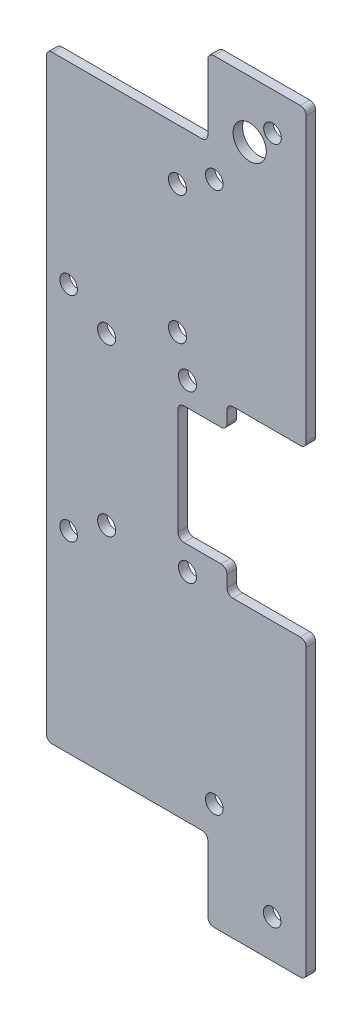
SolidWorks part; units mm, degrees
material "Thornel Mat VMA"
ref_plane "Front Plane" through (0, 0, 0) normal (0, 0, 1) x (1, 0, 0)
ref_plane "Top Plane" through (0, 0, 0) normal (0, 1, 0) x (1, 0, 0)
ref_plane "Right Plane" through (0, 0, 0) normal (1, 0, 0) x (0, 0, -1)
sketch "Sketch1" plane through (0, 0, 0) normal (0, 0, 1) x (1, 0, 0)
  line L0 (-2.9301, -104.5098) -> (-3.3149, -104.5098)
  line L1 (-3.3149, -72.8868) -> (-2.9301, -72.8868)
  line L78 (45.3299, -66.5368) -> (45.3299, -72.8868)
  line L79 (45.3299, -104.5098) -> (45.3299, -110.8598)
  line L80 (66.5174, -66.5368) -> (105.3971, 12.1397)
  line L81 (105.3971, 12.1397) -> (38.7094, 12.1397)
  line L88 (38.7094, 12.1397) -> (38.7094, -8.6883)
  line L89 (-2.9301, -8.6883) -> (38.7094, -8.6883)
  line L90 (-3.3149, -53.8368) -> (-2.9301, -53.8368)
  line L91 (-2.9301, -53.8368) -> (-2.9301, -8.6883)
  line L92 (-3.3149, -66.5368) -> (-3.3149, -53.8368)
  line L93 (-3.3149, -72.8868) -> (-3.3149, -66.5368)
  line L94 (-2.9301, -104.5098) -> (-2.9301, -72.8868)
  line L95 (-3.3149, -110.8598) -> (-3.3149, -104.5098)
  line L96 (66.5174, -110.8598) -> (105.3971, -189.5363)
  line L97 (105.3971, -189.5363) -> (38.7094, -189.5363)
  line L98 (38.7094, -189.5363) -> (38.7094, -168.7083)
  line L99 (-2.9301, -168.7083) -> (38.7094, -168.7083)
  line L106 (-3.3149, -110.8598) -> (-3.3149, -123.5598)
  line L107 (-3.3149, -123.5598) -> (-2.9301, -123.5598)
  line L108 (66.5174, -110.8598) -> (45.3299, -110.8598)
  line L109 (45.3299, -66.5368) -> (66.5174, -66.5368)
  line L110 (45.3299, -104.5098) -> (45.3299, -72.8868)
  line L111 (-2.9301, -123.5598) -> (-2.9301, -168.7083)
  circle A0 centre (90.6739, 2.6147) radius 2.3495
  circle A1 centre (41.9566, -16.4353) radius 2.3495
  circle A2 centre (3.0351, -60.1868) radius 2.3495
  circle A3 centre (3.0351, -117.2098) radius 2.3495
  circle A4 centre (41.9566, -160.9613) radius 2.3495
  circle A5 centre (90.6739, -180.0113) radius 2.3495
  circle A6 centre (51.4094, -3.1003) radius 4.445
  point P2 (90.6739, 2.6147)
  point P4 (41.9566, -16.4353)
  point P6 (3.0351, -60.1868)
  point P8 (3.0351, -117.2098)
  point P10 (41.9566, -160.9613)
  point P11 (90.6739, -180.0113)
  dimension "D2" = 4.699
  dimension "D5" = 8.89
  dimension "D1" = 66.6876
  dimension "D3" = 12.7
  dimension "D4" = 15.24
  dimension "D6" = 48.26
extrude "Boss-Extrude1" add sketch "Sketch1" along normal blind 2.54
sketch "Sketch2" plane through (0, 0, 2.54) normal (0, 0, 1) x (1, 0, 0)
  line L0 (-3.3149, -53.8368) -> (-3.3149, -72.8868) construction
  line L1 (45.3299, -66.5368) -> (66.5174, -66.5368) construction
  line L2 (45.3299, -88.6983) -> (-2.9301, -88.6983) construction
  line L3 (45.3299, -110.8598) -> (45.3299, -66.5368) construction
  line L4 (-2.9301, -72.8868) -> (-2.9301, -104.5098) construction
  circle A0 centre (13.1951, -66.5368) radius 2.413
  circle A2 centre (34.7851, -66.5368) radius 2.413
  circle A4 centre (34.7851, -110.8598) radius 2.413
  circle A6 centre (13.1951, -110.8598) radius 2.413
  dimension "D1" = 4.826
  dimension "D2" = 21.59
  dimension "D3" = 4.826
  dimension "D5" = 16.51
  dimension "D7" = 0
extrude "Cut-Extrude1" cut sketch "Sketch2" against normal through all
sketch "Sketch3" plane through (0, 0, 2.54) normal (0, 0, 1) x (1, 0, 0)
  line L0 (45.3299, -110.8598) -> (45.3299, -66.5368) construction
  line L1 (45.3299, -72.8868) -> (32.2451, -72.8868)
  line L2 (45.3299, -72.8868) -> (45.3299, -104.5098)
  line L3 (45.3299, -104.5098) -> (32.2451, -104.5098)
  line L4 (32.2451, -72.8868) -> (32.2451, -104.5098)
  line L5 (45.3299, -66.5368) -> (66.5174, -66.5368) construction
  line L6 (66.5174, -110.8598) -> (45.3299, -110.8598) construction
  circle A1 centre (13.1951, -66.5368) radius 2.413 construction
  dimension "D3" = 19.05
  dimension "D1" = 6.35
  dimension "D2" = 6.35
extrude "Cut-Extrude2" cut sketch "Sketch3" against normal through all
sketch "Sketch4" plane through (0, 0, 2.54) normal (0, 0, 1) x (1, 0, 0)
  line L0 (-2.9301, -168.7083) -> (38.7094, -168.7083) construction
  line L1 (27.4577, 15.7469) -> (40.2334, 15.7469)
  line L2 (27.4577, 15.7469) -> (27.4577, -8.6883)
  line L3 (27.4577, -8.6883) -> (40.2334, -8.6883)
  line L4 (40.2334, 15.7469) -> (40.2334, -8.6883)
  line L5 (0, -197.042) -> (40.2334, -197.042)
  line L6 (0, -197.042) -> (0, -168.7083)
  line L7 (0, -168.7083) -> (40.2334, -168.7083)
  line L8 (40.2334, -197.042) -> (40.2334, -168.7083)
  line L9 (38.7094, -168.7083) -> (38.7094, -189.5363) construction
  line L10 (38.7094, -8.6883) -> (-2.9301, -8.6883) construction
  dimension "D1" = 1.524
extrude "Cut-Extrude3" cut sketch "Sketch4" against normal through all
sketch "Sketch5" plane through (0, 0, 0) normal (0, 0, -1) x (-1, 0, 0)
  line L0 (2.9301, -8.6883) -> (2.9301, -53.8368) construction
  line L1 (-40.2334, -8.6883) -> (2.9301, -8.6883) construction
  circle A0 centre (-32.1219, -22.4043) radius 2.413
  circle A1 centre (-32.1219, -56.6943) radius 2.413
  dimension "D4" = 4.826
  dimension "D1" = 35.052
  dimension "D2" = 13.716
  dimension "D3" = 34.29
extrude "Cut-Extrude4" cut sketch "Sketch5" against normal through all
sketch "Sketch7" plane through (0, 0, 2.54) normal (0, 0, 1) x (1, 0, 0)
  line L0 (66.5174, -66.5368) -> (66.5174, 21.5221)
  line L1 (66.5174, 21.5221) -> (127.8208, 21.5221)
  line L2 (66.5174, -110.8598) -> (66.5174, -200.2563)
  line L3 (66.5174, -200.2563) -> (115.7822, -200.2563)
  line L4 (115.7822, -200.2563) -> (127.8208, 21.5221)
  line L5 (66.5174, -66.5368) -> (66.5174, -110.8598)
extrude "Cut-Extrude5" cut sketch "Sketch7" against normal through all both and the other way through all
extrude "Cut-Extrude6" cut sketch "Sketch8" against normal through all
sketch "Sketch8" plane through (-2.1864, -156.0179, 0) normal (0, 0, -1) x (0.9999, -0.0134, 0)
  circle A0 centre (57.5716, -158.8222) radius 2.3495
  circle A1 centre (59.8998, 22.5177) radius 2.3495
fillet "Fillet1" radius 1.5875 16 edges at (-2.9301, -168.7083, 1.27) (40.2334, -168.7083, 1.27) (40.2334, -189.5363, 1.27) (66.5174, -189.5363, 1.27) (66.5174, -110.8598, 1.27) (45.3299, -110.8598, 1.27) (45.3299, -104.5098, 1.27) (32.2451, -104.5098, 1.27) (32.2451, -72.8868, 1.27) (45.3299, -72.8868, 1.27) (45.3299, -66.5368, 1.27) (66.5174, -66.5368, 1.27) (66.5174, 12.1397, 1.27) (40.2334, 12.1397, 1.27) (40.2334, -8.6883, 1.27) (-2.9301, -8.6883, 1.27)
sketch "Sketch9" plane through (0, -123.5598, 0) normal (0, -1, 0) x (1, 0, 0)
  line L1 (-3.3149, 2.54) -> (-2.9301, 2.54)
  line L2 (-3.3149, 2.54) -> (-3.3149, 0)
  line L3 (-3.3149, 0) -> (-2.9301, 0)
  line L4 (-2.9301, 2.54) -> (-2.9301, 0)
extrude "Cut-Extrude7" cut sketch "Sketch9" against normal through all
